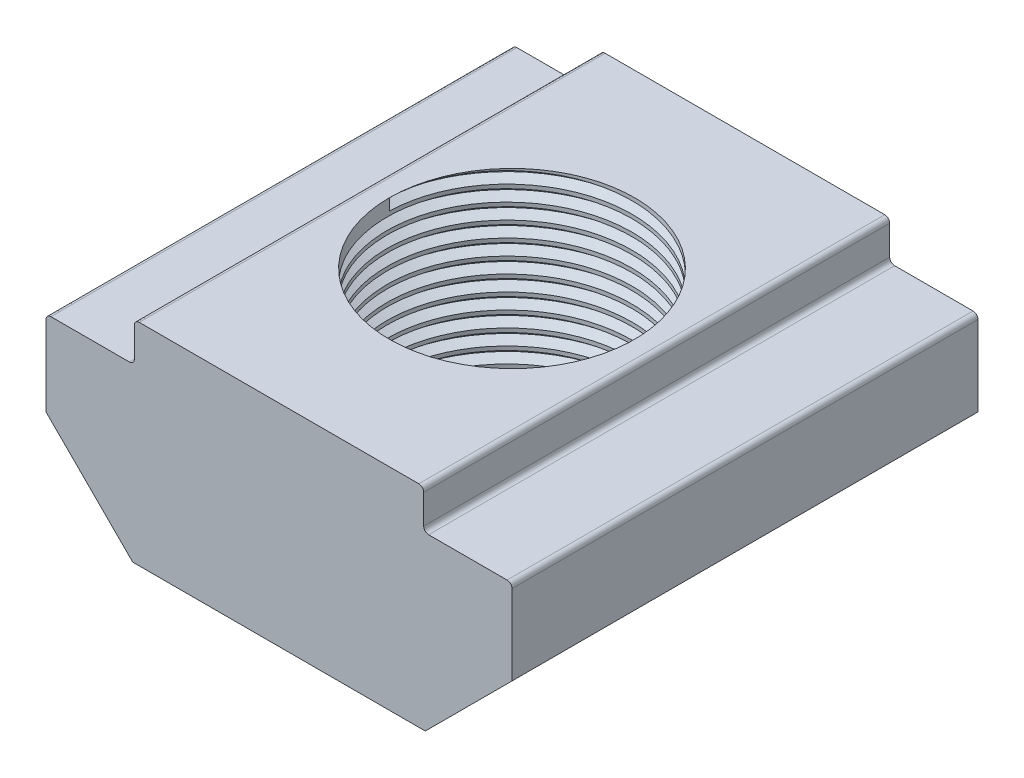
SolidWorks part; units mm, degrees
ref_plane "前视基准面" through (0, 0, 0) normal (0, 0, 1) x (1, 0, 0)
ref_plane "上视基准面" through (0, 0, 0) normal (0, 1, 0) x (1, 0, 0)
ref_plane "右视基准面" through (0, 0, 0) normal (1, 0, 0) x (0, 0, -1)
sketch "草图1" plane through (0, 0, 0) normal (0, 0, 1) x (1, 0, 0)
  line L0 (0, 0) -> (4.4896, 0) construction
  line L1 (0, 0) -> (0, 3.3646) construction
  line L2 (2.9822, 0) -> (-2.9822, 0)
  line L3 (-2.9822, 0) -> (-4.75, 1.7678)
  line L4 (-4.75, 1.7678) -> (-4.75, 3.5)
  line L5 (-4.75, 3.5) -> (-2.95, 3.5)
  line L6 (-2.95, 3.5) -> (-2.95, 4.3)
  line L7 (-2.95, 4.3) -> (2.95, 4.3)
  line L8 (2.95, 3.5) -> (2.95, 4.3)
  line L9 (4.75, 3.5) -> (2.95, 3.5)
  line L10 (4.75, 1.7678) -> (4.75, 3.5)
  line L11 (2.9822, 0) -> (4.75, 1.7678)
  point P14 (0, 4.3)
  point P18 (0, 0)
  dimension "D1" = 9.5
  dimension "D2" = 3.5
  dimension "D3" = 4.3
  dimension "D4" = 5.9
  dimension "D5" = 135
  dimension "D6" = 2.5
extrude "凸台-拉伸1" add sketch "草图1" against normal blind 9.5
sketch "草图2" plane through (0, 4.3, 0) normal (0, 1, 0) x (1, 0, 0)
  line L0 (0, 8.9805) -> (0, -1.8967) construction
  line L1 (-6.2198, 4.75) -> (8.7166, 4.75) construction
  line L4 (2.95, 9.5) -> (-2.95, 9.5) construction
  point P8 (0, 4.75)
  dimension "D1" = 4.75
hole_wizard "Ø5.0mm 暗销孔1" positions "草图2" profile "草图3" hole size "Ø5.0" standard "BSI" end condition through all
sketch "草图3" plane through (0, 4.3, -4.75) normal (1, 0, 0) x (0, 0, 1)
  line L0 (0, 0) -> (0, 4.3)
  line L1 (0, 4.3) -> (2.5, 4.3)
  line L2 (2.5, 4.3) -> (2.5, 0)
  line L5 (2.5, 0) -> (0, 0)
  line L11 (0, -6.35) -> (0, 107.95) construction
  dimension "通孔孔直径" = 5
  dimension "通孔孔深度" = 4.3
thread "螺纹线1" pitch 0.3175 method cut profile "螺纹线轮廓1" start angle 0, offset 0, length 4.3, pitch 0.3175, diameter 5
ref_plane "基准面4" through (-2.5, 4.3, -4.75) normal (0, 0, 1) x (-1, 0, 0)
sketch "螺纹线轮廓1" plane through (-2.5, 4.3, -4.75) normal (0, 0, 1) x (-1, 0, 0)
  line L0 (0, 0) -> (0, 0.3175) construction
  line L1 (0, 0) -> (0.1719, 0.0992)
  line L2 (0.1719, 0.0992) -> (0.1719, 0.1389)
  line L3 (0.1719, 0.1389) -> (0, 0.2381)
  line L4 (0.1719, 0.1191) -> (0, 0.1191) construction
  line L11 (0, 0) -> (0, 0.2381)
  point P2 (0, 0)
  dimension "Pitch" = 0.3175
  dimension "Profile_Angle" = 60
  dimension "Profile_Land" = 0.0397
  dimension "Profile_Height" = 0.1719
fillet "圆角1" radius 0.1 6 edges at (-2.95, 3.5, -4.75) (2.95, 3.5, -4.75) (4.75, 3.5, -4.75) (-4.75, 3.5, -4.75) (-2.95, 4.3, -4.75) (2.95, 4.3, -4.75)
